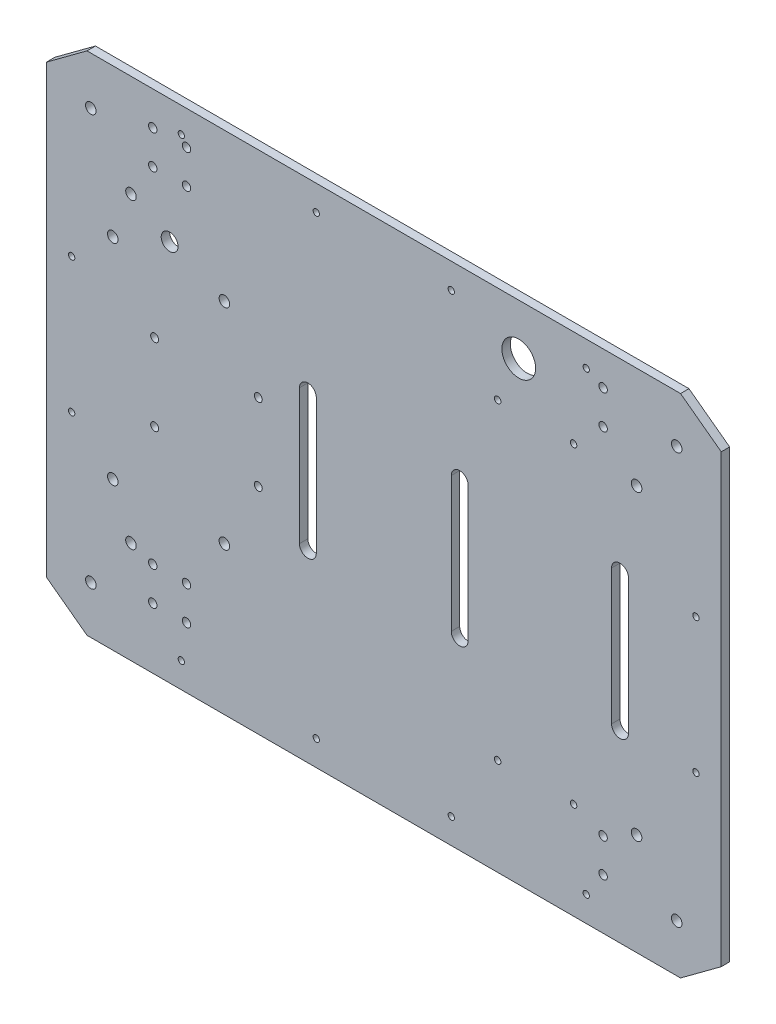
SolidWorks part; units mm, degrees
material "Thornel Mat VMA"
ref_plane "Front Plane" through (0, 0, 0) normal (0, 0, 1) x (1, 0, 0)
ref_plane "Top Plane" through (0, 0, 0) normal (0, 1, 0) x (1, 0, 0)
ref_plane "Right Plane" through (0, 0, 0) normal (1, 0, 0) x (0, 0, -1)
sketch "Sketch1" plane through (0, 0, 0) normal (0, 0, 1) x (1, 0, 0)
  line L0 (-127, 0) -> (127, 0) construction
  line L1 (0, -95.25) -> (0, 95.25) construction
  line L2 (-107.95, 0) -> (-107.95, 41.011) construction
  line L3 (-107.95, 41.011) -> (-95.25, 41.011) construction
  line L4 (-95.25, 41.011) -> (-79.9365, 52.3423) construction
  line L5 (-79.9365, 52.3423) -> (-79.9365, 76.2) construction
  line L6 (-79.9365, 76.2) -> (0, 76.2) construction
  line L7 (-95.25, 41.011) -> (-127, 83.9186) construction
  line L8 (-79.9365, 52.3423) -> (-111.6865, 95.25) construction
  line L9 (-111.6865, -95.25) -> (-127, -83.9186)
  line L10 (111.6865, -95.25) -> (127, -83.9186)
  line L11 (111.6865, 95.25) -> (127, 83.9186)
  line L12 (-87.5933, 46.6767) -> (-95.1475, 56.8856) construction
  line L13 (-95.1475, 56.8856) -> (-110.256, 77.3036) construction
  line L24 (127, -83.9186) -> (127, 83.9186)
  line L26 (111.6865, 95.25) -> (-111.6865, 95.25)
  line L27 (-111.6865, 95.25) -> (-127, 83.9186)
  line L28 (-127, 83.9186) -> (-127, -83.9186)
  line L30 (-111.6865, -95.25) -> (111.6865, -95.25)
  circle A0 centre (-95.1475, 56.8856) radius 1.9844
  circle A1 centre (-110.256, 77.3036) radius 1.9844
  circle A2 centre (110.256, 77.3036) radius 1.9844
  circle A3 centre (95.1475, 56.8856) radius 1.9844
  circle A4 centre (-110.256, -77.3036) radius 1.9844
  circle A5 centre (-95.1475, -56.8856) radius 1.9844
  circle A6 centre (110.256, -77.3036) radius 1.9844
  circle A7 centre (95.1475, -56.8856) radius 1.9844
  point P12 (0, 0)
  dimension "D10" = 3.9688
  dimension "D11" = 3.9688
  dimension "D1" = 190.5
  dimension "D2" = 254
  dimension "D3" = 19.05
  dimension "D4" = 19.05
  dimension "D5" = 12.7
  dimension "D6" = 19.05
  dimension "D7" = 143.5
  dimension "D8" = 12.7
  dimension "D9" = 25.4
extrude "Boss-Extrude1" add sketch "Sketch1" along normal blind 3.175
sketch "Sketch2" plane through (0, 0, 3.175) normal (0, 0, 1) x (1, 0, 0)
  line L0 (-127, 0) -> (127, 0) construction
  line L1 (-127, 83.9186) -> (-127, -83.9186) construction
  line L2 (127, -83.9186) -> (127, 83.9186) construction
  line L3 (57.15, 65.0875) -> (57.15, -65.0875) construction
  line L4 (38.1, 65.0875) -> (76.2, 65.0875)
  line L5 (38.1, 65.0875) -> (38.1, -65.0875)
  line L6 (38.1, -65.0875) -> (76.2, -65.0875)
  line L7 (76.2, 65.0875) -> (76.2, -65.0875)
  line L8 (38.1, 65.0875) -> (76.2, -65.0875) construction
  line L9 (38.1, -65.0875) -> (76.2, 65.0875) construction
  line L10 (57.15, 58.7375) -> (47.625, 58.7375) construction
  line L11 (47.625, 58.7375) -> (38.1, 58.7375) construction
  circle A0 centre (42.8625, 58.7375) radius 1.2136
  circle A1 centre (42.8625, -58.7375) radius 1.2136
  circle A2 centre (71.4375, -58.7375) radius 1.2136
  circle A3 centre (71.4375, 58.7375) radius 1.2136
  point P6 (57.15, 0)
  point P17 (42.8625, 58.7375)
  dimension "D1" = 38.1
  dimension "D2" = 130.175
  dimension "D3" = 6.35
  dimension "D4" = 9.525
  dimension "D5" = 69.85
extrude "Cut-Extrude1" cut sketch "Sketch2" against normal through all contours A1 | A2 | A3 | A0 region at (42.8625, 58.7375, 3.175) region at (42.8625, -58.7375, 3.175) region at (71.4375, -58.7375, 3.175) region at (71.4375, 58.7375, 3.175)
sketch "Sketch3" plane through (0, 0, 3.175) normal (0, 0, 1) x (1, 0, 0)
  line L0 (0, 95.25) -> (0, -95.25) construction
  line L1 (111.6865, 95.25) -> (-111.6865, 95.25) construction
  line L2 (-111.6865, -95.25) -> (111.6865, -95.25) construction
  line L3 (127, 0) -> (-127, 0) construction
  line L4 (127, -83.9186) -> (127, 83.9186) construction
  line L5 (-127, 83.9186) -> (-127, -83.9186) construction
  line L8 (119.3433, -89.5843) -> (111.789, -79.3753) construction
  line L10 (111.6865, -95.25) -> (127, -83.9186) construction
  line L11 (111.6865, -95.25) -> (127, -83.9186)
  circle A0 centre (111.789, -79.3753) radius 1.9844
  circle A1 centre (96.6805, -58.9574) radius 1.9844
  dimension "D2" = 3.9688
  dimension "D3" = 3.9688
  dimension "D1" = 12.7
  dimension "D4" = 25.4
sketch "Sketch5" plane through (0, 0, 0) normal (0, 0, -1) x (-1, 0, 0)
  line L0 (-127, 0) -> (127, 0) construction
  line L1 (105.9946, 43.5) -> (55.9947, 43.5) construction
  line L2 (105.9946, 43.5) -> (105.9946, -43.5) construction
  line L3 (105.9946, -43.5) -> (55.9947, -43.5) construction
  line L4 (55.9947, 43.5) -> (55.9947, -43.5) construction
  line L5 (105.9946, 43.5) -> (55.9947, -43.5) construction
  line L6 (105.9946, -43.5) -> (55.9947, 43.5) construction
  line L8 (0, 64.0679) -> (0, -49.8393) construction
  line L9 (-47.625, 22.225) -> (47.625, 22.225) construction
  line L10 (-47.625, 22.225) -> (-47.625, -22.225) construction
  line L11 (-47.625, -22.225) -> (47.625, -22.225) construction
  line L12 (47.625, 22.225) -> (47.625, -22.225) construction
  line L13 (-47.625, 22.225) -> (47.625, -22.225) construction
  line L14 (-47.625, -22.225) -> (47.625, 22.225) construction
  line L15 (-88.9, 25.4) -> (-88.9, -25.4) construction
  line L16 (-85.725, 25.4) -> (-85.725, -25.4)
  line L17 (-92.075, 25.4) -> (-92.075, -25.4)
  line L18 (111.6865, -95.25) -> (-111.6865, -95.25) construction
  line L19 (-28.575, 25.4) -> (-28.575, -25.4) construction
  line L20 (-111.6865, 95.25) -> (111.6865, 95.25) construction
  line L21 (-127, -83.9186) -> (-127, 83.9186) construction
  line L22 (-50.8, 76.2) -> (80.5946, 76.2) construction
  line L23 (80.5946, 76.2) -> (80.5946, 48.58) construction
  line L24 (-127, -83.9186) -> (-127, 83.9186) construction
  line L25 (80.5946, -77.0458) -> (80.5946, 48.58) construction
  line L26 (127, 0) -> (-127, 0) construction
  line L27 (80.9947, 0) -> (80.9947, -8419.0368) construction
  line L28 (-25.4, 25.4) -> (-25.4, -25.4)
  line L29 (-31.75, 25.4) -> (-31.75, -25.4)
  line L30 (28.575, 25.4) -> (28.575, -25.4) construction
  line L31 (25.4, 25.4) -> (25.4, -25.4)
  line L32 (31.75, 25.4) -> (31.75, -25.4)
  line L33 (66.7369, 0) -> (66.7369, 12.9123) construction
  line L34 (44.2369, 17.5) -> (89.2369, 17.5)
  line L35 (44.2369, 17.5) -> (44.2369, -17.5)
  line L36 (44.2369, -17.5) -> (89.2369, -17.5)
  line L37 (89.2369, 17.5) -> (89.2369, -17.5)
  line L38 (44.2369, 17.5) -> (89.2369, -17.5) construction
  line L39 (44.2369, -17.5) -> (89.2369, 17.5) construction
  arc A0 (-85.725, 25.4) -> (-92.075, 25.4) centre (-88.9, 25.4) ccw
  arc A1 (-92.075, -25.4) -> (-85.725, -25.4) centre (-88.9, -25.4) ccw
  circle A2 centre (80.5946, 48.58) radius 3.175
  circle A3 centre (-50.8, 76.2) radius 6.35
  circle A4 centre (74.2446, 69.85) radius 1.5875
  circle A5 centre (74.2446, 82.55) radius 1.5875
  circle A6 centre (74.2446, -72.39) radius 1.5875
  circle A7 centre (74.2446, -59.69) radius 1.5875
  circle A8 centre (86.9446, -72.39) radius 1.5875
  circle A9 centre (86.9446, -59.69) radius 1.5875
  circle A10 centre (86.9446, 82.55) radius 1.5875
  circle A11 centre (86.9446, 69.85) radius 1.5875
  circle A12 centre (59.9952, 39.4995) radius 1.9844
  circle A13 centre (101.9941, 39.4995) radius 1.9844
  circle A14 centre (59.9952, -39.4995) radius 1.9844
  circle A15 centre (101.9941, -39.4995) radius 1.9844
  circle A16 centre (-82.55, -63.4824) radius 1.5875
  circle A17 centre (-82.55, -76.1824) radius 1.5875
  circle A18 centre (-82.55, 82.55) radius 1.5875
  circle A19 centre (-82.55, 69.85) radius 1.5875
  arc A20 (-25.4, 25.4) -> (-31.75, 25.4) centre (-28.575, 25.4) ccw
  arc A21 (-31.75, -25.4) -> (-25.4, -25.4) centre (-28.575, -25.4) ccw
  arc A22 (25.4, 25.4) -> (31.75, 25.4) centre (28.575, 25.4) cw
  arc A23 (31.75, -25.4) -> (25.4, -25.4) centre (28.575, -25.4) cw
  circle A24 centre (47.2369, 14.5) radius 1.5
  circle A25 centre (47.2369, -14.5) radius 1.5
  circle A26 centre (86.2369, -14.5) radius 1.5
  circle A27 centre (86.2369, 14.5) radius 1.5
  point P0 (80.9947, 0)
  point P9 (0, 0)
  point P16 (-88.9, 0)
  point P77 (-28.575, 0)
  point P84 (28.575, 0)
  point P89 (66.7369, 0)
  dimension "D10" = 6.35
  dimension "D15" = 12.7
  dimension "D17" = 3.175
  dimension "D18" = 3.175
  dimension "D21" = 3.175
  dimension "D22" = 3.175
  dimension "D25" = 4.0005
  dimension "D27" = 3.9688
  dimension "D28" = 3.175
  dimension "D29" = 3.175
  dimension "D30" = 12.7
  dimension "D33" = 3.175
  dimension "D34" = 3.175
  dimension "D45" = 3
  dimension "D1" = 87.0001
  dimension "D2" = 49.9999
  dimension "D4" = 44.45
  dimension "D5" = 95.25
  dimension "D6" = 50.8
  dimension "D7" = 6.35
  dimension "D8" = 38.1
  dimension "D11" = 5.08
  dimension "D12" = 25.4
  dimension "D13" = 19.05
  dimension "D14" = 76.2
  dimension "D16" = 12.7
  dimension "D19" = 6.35
  dimension "D20" = 12.7
  dimension "D23" = 12.7
  dimension "D24" = 22.86
  dimension "D26" = 4.0005
  dimension "D32" = 44.45
  dimension "D35" = 12.7
  dimension "D36" = 6.35
  dimension "D37" = 44.45
  dimension "D38" = 50.8
  dimension "D39" = 6.35
  dimension "D40" = 28.575
  dimension "D41" = 45
  dimension "D42" = 35
  dimension "D43" = 3
  dimension "D44" = 3
extrude "Cut-Extrude2" cut sketch "Sketch5" against normal through all contours A3 | A2 | A5 | A4 | A6 | A7 | A8 | A9 | A10 | A11 | A14 | A15 | A13 | A12 | A19 | A18 | A17 | A16 | L29 A21 L28 A20 | A23 L4 A22 L31 | A23 L32 A22 L4 | A27 | A24 | A25 | A26 | L17 A1 L16 A0 | A4 | A19 region at (88.9, 0, 0) region at (28.575, 0, 0) region at (-28.575, 0, 0) region at (-80.5946, 48.58, 0) region at (50.8, 76.2, 0) region at (-74.2446, 69.85, 0) region at (-74.2446, 82.55, 0) region at (-74.2446, -72.39, 0) region at (-74.2446, -59.69, 0) region at (-86.9446, -72.39, 0) region at (-86.9446, -59.69, 0) region at (-86.9446, 82.55, 0) region at (-86.9446, 69.85, 0) region at (-59.9952, 39.4995, 0) region at (-101.9941, 39.4995, 0) region at (-59.9952, -39.4995, 0) region at (-101.9941, -39.4995, 0) region at (82.55, -63.4824, 0) region at (82.55, -76.1824, 0) region at (82.55, 82.55, 0) region at (82.55, 69.85, 0) region at (-47.2369, 14.5, 0) region at (-47.2369, -14.5, 0) region at (-86.2369, -14.5, 0) region at (-86.2369, 14.5, 0)
sketch "Sketch6" plane through (0, 0, 0) normal (0, 0, -1) x (-1, 0, 0)
  line L0 (0, 0) -> (-135.1326, 0) construction
  line L1 (0, 0) -> (0, -95.25) construction
  line L2 (111.6865, -95.25) -> (-111.6865, -95.25) construction
  line L3 (-76.2, -95.25) -> (-76.2, -85.725) construction
  line L4 (117.475, 0) -> (117.475, -25.4) construction
  line L5 (127, 0) -> (-127, 0) construction
  line L6 (127, 83.9186) -> (127, -83.9186) construction
  circle A0 centre (-76.2, -85.725) radius 1.1906
  circle A1 centre (-25.4, -85.725) radius 1.1906
  circle A2 centre (25.4, -85.725) radius 1.1906
  circle A3 centre (76.2, -85.725) radius 1.1906
  circle A4 centre (76.2, 85.725) radius 1.1906
  circle A5 centre (25.4, 85.725) radius 1.1906
  circle A6 centre (-25.4, 85.725) radius 1.1906
  circle A7 centre (-76.2, 85.725) radius 1.1906
  circle A8 centre (117.475, -25.4) radius 1.1906
  circle A9 centre (117.475, 25.4) radius 1.1906
  circle A10 centre (-117.475, 25.4) radius 1.1906
  circle A11 centre (-117.475, -25.4) radius 1.1906
  dimension "D1" = 2.3813
  dimension "D7" = 2.3813
  dimension "D2" = 9.525
  dimension "D3" = 76.2
  dimension "D5" = 9.525
  dimension "D6" = 25.4
  dimension "D4" = 4
extrude "Cut-Extrude3" cut sketch "Sketch6" against normal through all
